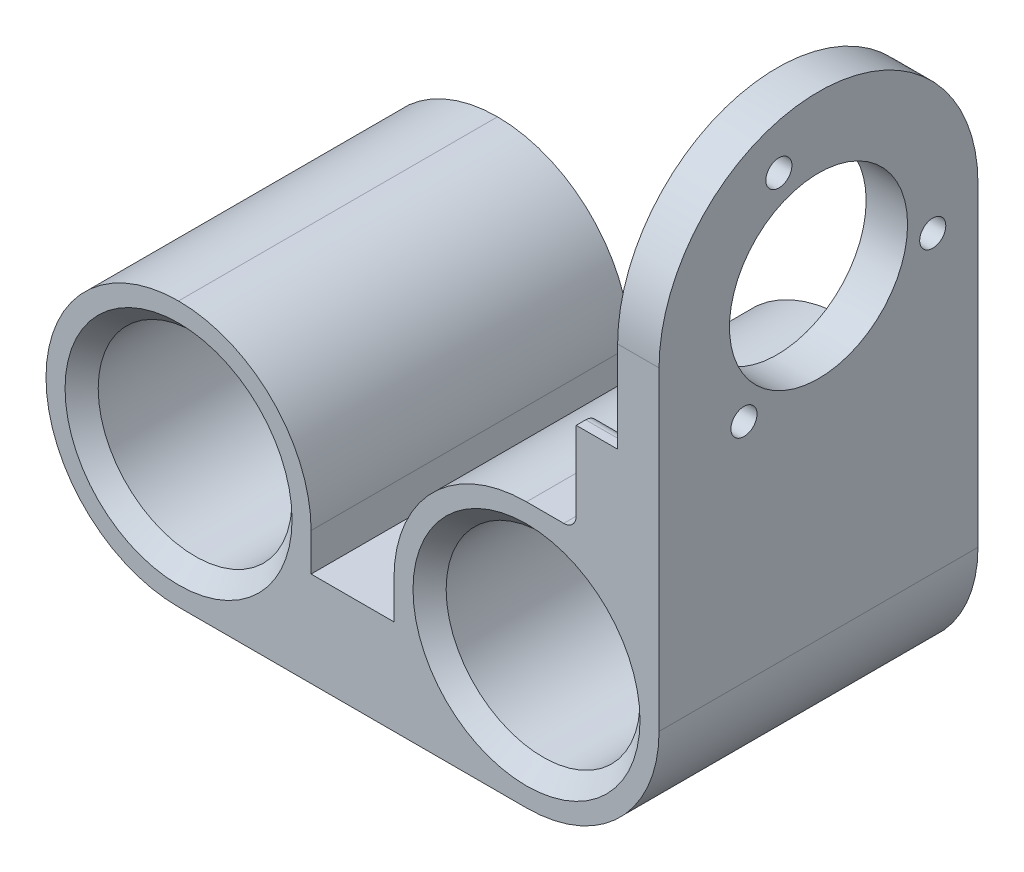
SolidWorks part; units mm, degrees
material "ABS"
ref_plane "Front Plane" through (0, 0, 0) normal (0, 0, 1) x (1, 0, 0)
ref_plane "Top Plane" through (0, 0, 0) normal (0, 1, 0) x (1, 0, 0)
ref_plane "Right Plane" through (0, 0, 0) normal (1, 0, 0) x (0, 0, -1)
sketch "Sketch1" plane through (0, 0, 0) normal (0, 0, 1) x (1, 0, 0)
  line L1 (0, 0) -> (74, 0)
  line L2 (0, 0) -> (0, 32)
  line L3 (0, 32) -> (74, 32)
  line L4 (74, 0) -> (74, 32)
  circle A0 centre (16, 16) radius 11.7
  circle A1 centre (58, 16) radius 11.7
  point P9 (0, 16)
  dimension "D1" = 23.4
  dimension "D2" = 23.4
  dimension "D3" = 42
  dimension "D4" = 16
  dimension "D5" = 16
  dimension "D6" = 16
  dimension "D7" = 16
extrude "Boss-Extrude1" add sketch "Sketch1" along normal blind 38.5
sketch "Sketch2" plane through (74, 0, 0) normal (1, 0, 0) x (0, 0, -1)
  line L0 (-19.25, 54) -> (-5.4627, 51.5689) construction
  line L1 (-19.25, 73.25) -> (-19.25, 34.75) construction
  line L2 (-38.5, 32) -> (0, 32) construction
  line L3 (-19.25, 54) -> (-6.0943, 58.7883) construction
  line L4 (0, 32) -> (0, 54)
  line L5 (-38.5, 32) -> (-38.5, 54)
  line L7 (-38.5, 32) -> (0, 32)
  line L8 (-38.5, 32) -> (-38.5, 0)
  line L9 (-38.5, 0) -> (0, 0)
  line L10 (0, 32) -> (0, 0)
  circle A0 centre (-19.25, 54) radius 19.25
  circle A1 centre (-19.25, 54) radius 14 construction
  circle A5 centre (-5.4627, 51.5689) radius 1.575
  circle A10 centre (-19.25, 54) radius 10.75
  circle A11 centre (-28.249, 43.2754) radius 1.575
  circle A13 centre (-24.0383, 67.1557) radius 1.575
  point P3 (-6.0943, 58.7883)
  point P11 (-19.25, 32)
  point P26 (-19.25, 54)
  point P32 (-19.25, 54)
  dimension "D1" = 38.5
  dimension "D2" = 28
  dimension "D4" = 100
  dimension "D6" = 3
  dimension "D7" = 22
  dimension "D8" = 21.5
  dimension "D9" = 3.15
  dimension "D5" = 30
extrude "Boss-Extrude2" add sketch "Sketch2" against normal blind 5
sketch "Sketch3" plane through (69, 0, 0) normal (-1, 0, 0) x (0, 0, 1)
  line L0 (0, 32) -> (0, 54)
  line L1 (0, 32) -> (38.5, 32)
  line L2 (38.5, 32) -> (38.5, 54)
  line L3 (0, 43) -> (38.5, 43)
  circle A0 centre (19.25, 54) radius 20.5
  dimension "D1" = 41
extrude "Boss-Extrude3" add sketch "Sketch3" along normal blind 5
sketch "Sketch4" plane through (0, 0, 0) normal (0, 0, -1) x (-1, 0, 0)
  line L0 (-46.3216, 15.2889) -> (-27.6784, 15.2889) construction
  line L1 (-7.8441, 7.6112) -> (-66.1559, 7.6112) construction
  line L2 (-37, 15.2889) -> (-37, 7.6112) construction
  line L3 (-46.3, 16) -> (-27.7, 16) construction
  line L4 (-42, 11.45) -> (-32, 11.45)
  line L5 (-42, -13.55) -> (-32, -13.55)
  line L6 (-42, -13.55) -> (-42, 36.45)
  line L7 (-42, 36.45) -> (-32, 36.45)
  line L8 (-32, -13.55) -> (-32, 36.45)
  line L9 (-42, -13.55) -> (-32, 36.45) construction
  line L10 (-42, 36.45) -> (-32, -13.55) construction
  circle A0 centre (-58, 16) radius 11.7 construction
  circle A1 centre (-16, 16) radius 11.7 construction
  point P13 (-37, 11.45)
  dimension "D1" = 10
  dimension "D2" = 25
extrude "Cut-Extrude1" cut sketch "Sketch4" against normal through all both and the other way through all
sketch "Sketch5" plane through (0, 11.45, 0) normal (0, 1, 0) x (1, 0, 0)
  line L0 (32, 0) -> (32, -38.5)
  line L6 (42, 0) -> (32, 0)
  circle A0 centre (37, -19.25) radius 2.15
  point P2 (37, 0)
  point P4 (32, -19.25)
  dimension "D1" = 4.3
extrude "Cut-Extrude2" cut sketch "Sketch5" against normal blind 18 contours A0
fillet "Fillet8" radius 16 5 edges at (42, 32, 19.25) (32, 32, 19.25) (0, 32, 19.25) (0, 0, 19.25) (74, 0, 19.25)
fillet "Fillet9" radius 1.5 3 edges at (66.5, 43, 1.9512) (66.5, 43, 36.5488) (64, 32, 19.25)
fillet "Fillet10" radius 2 4 edges at (69.7, 16, 38.5) (27.7, 16, 38.5) (27.7, 16, 0) (69.7, 16, 0) profile chamfer
sketch "Sketch6" plane through (0, 0, 0) normal (0, -1, 0) x (1, 0, 0)
  line L1 (39.1102, 15.4689) -> (41.3297, 19.1869)
  line L2 (41.3297, 19.1869) -> (39.2194, 22.9681)
  line L3 (39.2194, 22.9681) -> (34.8898, 23.0311)
  line L4 (34.8898, 23.0311) -> (32.6703, 19.3131)
  line L5 (32.6703, 19.3131) -> (34.7806, 15.5319)
  line L6 (34.7806, 15.5319) -> (39.1102, 15.4689)
  circle A0 centre (37, 19.25) radius 3.75 construction
  dimension "D1" = 7.5
extrude "Cut-Extrude3" cut sketch "Sketch6" against normal blind 3
